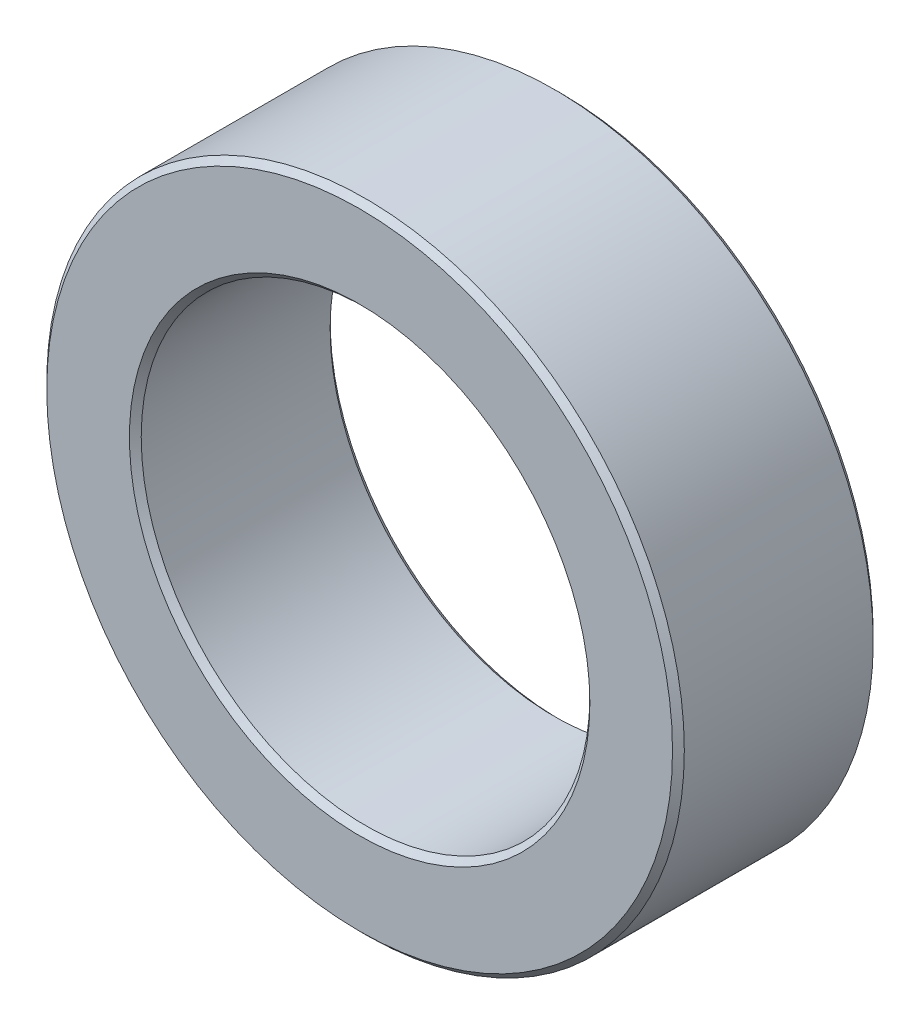
SolidWorks part; units mm, degrees
material "1.0037 (S235JR)"
ref_plane "E_Rechts" through (0, 0, 0) normal (0, 0, 1) x (1, 0, 0)
ref_plane "E_Oben" through (0, 0, 0) normal (0, 1, 0) x (1, 0, 0)
ref_plane "E_Vorne" through (0, 0, 0) normal (1, 0, 0) x (0, 0, -1)
ref_axis "A_Drehachse" through (0, 0, -88.99) along (0, 0, 1)
sketch "Skizze1" plane through (0, 0, 0) normal (0, 0, 1) x (1, 0, 0)
  circle A0 centre (0, 0) radius 19
  circle A1 centre (0, 0) radius 27
  dimension "D1" = 54
  dimension "D2" = 38
extrude "Aufsatz-Linear austragen1" add sketch "Skizze1" along normal mid plane 17
chamfer "Fase1" distance 0.5 angle 45 4 edges at (19, 0, -8.5) (27, 0, -8.5) (27, 0, 8.5) (19, 0, 8.5)
